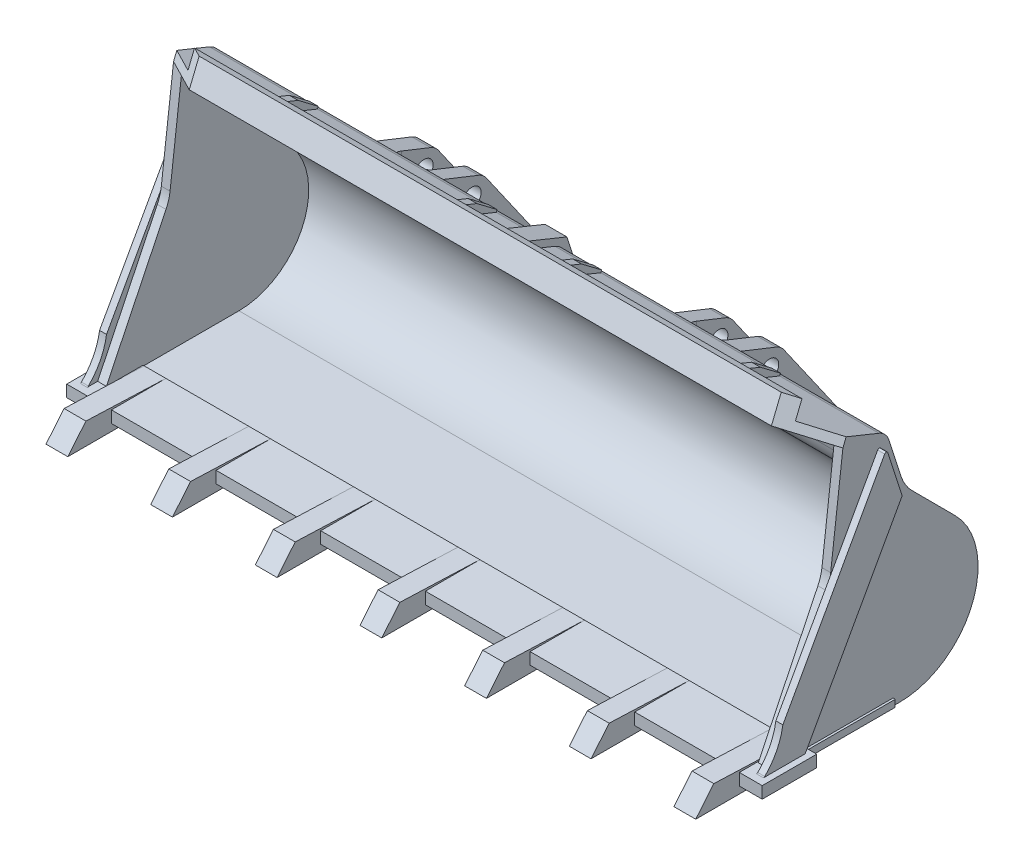
SolidWorks part; units mm, degrees
ref_plane "Front Plane" through (0, 0, 0) normal (0, 0, 1) x (1, 0, 0)
ref_plane "Top Plane" through (0, 0, 0) normal (0, 1, 0) x (1, 0, 0)
ref_plane "Right Plane" through (0, 0, 0) normal (1, 0, 0) x (0, 0, -1)
sketch "Sketch1" plane through (0, 0, 0) normal (1, 0, 0) x (0, 0, -1)
  line L0 (0, 0) -> (0, 1)
  line L1 (0, 1) -> (7.25, 16)
  line L2 (7.25, 16) -> (8.75, 28.5)
  line L3 (0, 0) -> (15.25, 0)
  line L4 (8.75, 28.5) -> (5.5533, 29.7974)
  line L5 (5.5533, 29.7974) -> (6.6814, 32.5772)
  line L6 (6.6814, 32.5772) -> (7.608, 32.2011)
  line L7 (7.608, 32.2011) -> (6.8559, 30.348)
  line L8 (6.8559, 30.348) -> (13.7401, 27.5539)
  line L9 (13.7401, 27.5539) -> (15.7923, 21.2039)
  line L10 (15.7923, 21.2039) -> (21.624, 15.3539)
  arc A0 (21.624, 15.3539) -> (15.25, 0) centre (15.25, 9) cw
  dimension "D15" = 9
  dimension "D1" = 1
  dimension "D2" = 7.25
  dimension "D3" = 16
  dimension "D4" = 28.5
  dimension "D5" = 8.75
  dimension "D6" = 15.25
  dimension "D7" = 2
  dimension "D8" = 1
  dimension "D9" = 3.45
  dimension "D10" = 1
  dimension "D11" = 130
  dimension "D12" = 153
  dimension "D13" = 6.35
  dimension "D14" = 5.85
extrude "Boss-Extrude1" add sketch "Sketch1" along normal blind 38.375
fillet "Fillet1" radius 5 1 edges at (19.1875, 21.2039, -15.7923)
fillet "Fillet2" radius 2 1 edges at (19.1875, 27.5539, -13.7401)
fillet "Fillet3" radius 5 1 edges at (19.1875, 16, -7.25)
shell "Shell1" thickness 1 removed face at (0, 19.8023, -10.049) removed face at (19.1875, 16.029, -7.1509) removed face at (19.1875, 22.6643, -8.0497) removed face at (19.1875, 8.1243, -3.4434) removed face at (19.1875, 0.5, 0)
sketch "Sketch3" plane through (0, 0, 0) normal (1, 0, 0) x (0, 0, -1)
  line L0 (0, 0) -> (15.25, 0) construction
  line L1 (4.25, 1.1) -> (-2, 1.1)
  line L2 (4.25, 1.1) -> (4.25, -0.25)
  line L3 (4.25, -0.25) -> (-2, -0.25)
  line L4 (-2, 1.1) -> (-2, -0.25)
  dimension "D1" = 2
  dimension "D2" = 1.35
  dimension "D3" = 6.25
  dimension "D4" = 0.25
extrude "Boss-Extrude2" add sketch "Sketch3" along normal blind 39.875
sketch "Sketch4" plane through (0, 0, 0) normal (1, 0, 0) x (0, 0, -1)
  line L1 (4.25, 0) -> (14.5, 0)
  line L2 (4.25, 0) -> (4.25, 0.8)
  line L3 (4.25, 0.8) -> (14.5, 0.8)
  line L4 (14.5, 0) -> (14.5, 0.8)
  dimension "D1" = 10.25
  dimension "D2" = 0.8
extrude "Boss-Extrude3" add sketch "Sketch4" along normal blind 38.625
sketch "Sketch5" plane through (38.375, 0, 0) normal (1, 0, 0) x (0, 0, -1)
  line L0 (-1.4, 0.8) -> (3.4593, 0.8)
  line L1 (3.4593, 0.8) -> (14.7517, 21.1721)
  line L2 (14.7517, 21.1721) -> (12.962, 26.7098)
  line L3 (12.962, 26.7098) -> (1.0667, 5.25)
  line L4 (15.4232, 22.3462) -> (14.0269, 26.6665) construction
  line L5 (-2, 1.1) -> (-2, -0.25) construction
  line L6 (4.25, 1.1) -> (-2, 1.1) construction
  line L8 (14.5, 0.8) -> (4.25, 0.8) construction
  line L9 (-1.4, 0.8) -> (1.0667, 5.25) construction
  arc A0 (1.0667, 5.25) -> (-1.4, 0.8) centre (-6.1511, 6.3423) cw
  dimension "D4" = 7.3
  dimension "D1" = 1
  dimension "D2" = 0.6
  dimension "D3" = 0.3
  dimension "D5" = 4.45
  dimension "D6" = 4.25
  dimension "D7" = 61
extrude "Boss-Extrude4" add sketch "Sketch5" along normal blind 0.8
fillet "Fillet4" radius 0.2 3 edges at (38.775, 1.1, 1.0709) (38.775, 21.1721, -14.7517) (38.775, 26.7098, -12.962)
sketch "Sketch6" plane through (0, 28.445, -11.5446) normal (0, 0.9266, -0.3761) x (1, 0, 0)
  line L0 (38.375, -2.6101) -> (33.375, -6.0601)
  line L1 (38.375, -6.0601) -> (0, -6.0601) construction
  line L2 (33.375, -6.0601) -> (38.375, -6.0601)
  line L3 (38.375, -6.0601) -> (38.375, -2.6101)
  dimension "D1" = 5
extrude "Cut-Extrude1" cut sketch "Sketch6" against normal up to next and the other way through all
sketch "Sketch7" plane through (0, 0, 0) normal (1, 0, 0) x (0, 0, -1)
  line L0 (9.1696, 29.4089) -> (9.4516, 30.1039)
  line L1 (9.4516, 30.1039) -> (14.2253, 28.1665)
  line L2 (14.2253, 28.1665) -> (15.568, 24.0118)
  line L3 (15.568, 24.0118) -> (14.9495, 23.8119)
  line L16 (4.25, 0) -> (15.25, 0)
  line L17 (4.25, -0.25) -> (4.25, 0)
  line L18 (-2, -0.25) -> (4.25, -0.25)
  line L19 (-2, 1.1) -> (-2, -0.25)
  line L20 (4.25, 1.1) -> (-2, 1.1)
  line L21 (4.25, 1) -> (4.25, 1.1)
  line L22 (15.25, 1) -> (4.25, 1)
  line L23 (15.9316, 19.6478) -> (20.9157, 14.648)
  line L24 (13.0754, 26.359) -> (14.4716, 22.0386)
  line L25 (5.5533, 29.7974) -> (12.4999, 26.9781)
  line L26 (6.6814, 32.5772) -> (5.5533, 29.7974)
  line L27 (7.608, 32.2011) -> (6.6814, 32.5772)
  line L28 (6.8559, 30.348) -> (7.608, 32.2011)
  line L29 (12.876, 27.9047) -> (6.8559, 30.348)
  line L30 (15.4232, 22.3462) -> (14.0269, 26.6665)
  line L31 (21.624, 15.3539) -> (16.6398, 20.3538)
  line L45 (12.876, 27.9047) -> (9.1696, 29.4089)
  line L46 (14.9495, 23.8119) -> (14.0269, 26.6665)
  arc A6 (15.25, 1) -> (20.9157, 14.648) centre (15.25, 9) ccw
  arc A7 (14.4716, 22.0386) -> (15.9316, 19.6478) centre (20.1809, 23.8838) ccw
  arc A8 (13.0754, 26.359) -> (12.4999, 26.9781) centre (12.1238, 26.0515) ccw
  arc A9 (14.0269, 26.6665) -> (12.876, 27.9047) centre (12.1238, 26.0515) ccw
  arc A10 (15.4232, 22.3462) -> (16.6398, 20.3538) centre (20.1809, 23.8838) ccw
  arc A11 (15.25, 0) -> (21.624, 15.3539) centre (15.25, 9) ccw
  arc A15 (14.0269, 26.6665) -> (12.876, 27.9047) centre (12.1238, 26.0515) ccw
  dimension "D2" = 0.75
  dimension "D3" = 0.65
  dimension "D4" = 4
  dimension "D5" = 3
  dimension "D1" = 0
extrude "Boss-Extrude5" add sketch "Sketch7" along normal blind 1.25
sketch "Sketch8" plane through (0, 28.445, -11.5446) normal (0, 0.9266, -0.3761) x (1, 0, 0)
  line L0 (38.375, 1.4368) -> (1.25, 1.4368) construction
  line L1 (5.5, 1.4368) -> (6.5, 1.4368)
  line L2 (5.5, 1.4368) -> (5.5, -5.0601)
  line L3 (5.5, -5.0601) -> (6.5, -5.0601)
  line L4 (6.5, 1.4368) -> (6.5, -5.0601)
  line L5 (34.8243, -5.0601) -> (0, -5.0601) construction
  line L6 (0, -2.5632) -> (0, -5.0601) construction
  line L7 (26, 1.4368) -> (27, 1.4368)
  line L8 (26, 1.4368) -> (26, -5.0601)
  line L9 (26, -5.0601) -> (27, -5.0601)
  line L10 (27, 1.4368) -> (27, -5.0601)
  dimension "D1" = 1
  dimension "D2" = 5.5
  dimension "D3" = 20.5
  dimension "D4" = 1
extrude "Boss-Extrude6" add sketch "Sketch8" along normal blind 1
chamfer "Chamfer1" distance 0.75 angle 75 2 edges at (26.5, 28.8313, -13.252) (6, 28.8313, -13.252) first distance on face at (26.5, 28.368, -13.064) first distance on face at (6, 28.368, -13.064)
mirror "Mirror1" about plane through (0, 0, 0) normal (1, 0, 0) of bodies 107
sketch "Sketch9" plane through (0, 0, 0) normal (1, 0, 0) x (0, 0, -1)
  line L0 (4.25, -0.25) -> (4.25, 1.1) construction
  line L2 (4.25, 0) -> (14.5, 0) construction
  line L3 (14.5, 0) -> (15.25, 0) construction
  line L4 (21.624, 15.3539) -> (16.6398, 20.3538) construction
  line L5 (15.4232, 22.3462) -> (14.0269, 26.6665) construction
  line L6 (4.25, -0.125) -> (4.25, 0)
  line L8 (4.25, 0) -> (14.5, 0)
  line L9 (14.5, 0) -> (15.25, 0)
  line L10 (21.624, 15.3539) -> (16.6398, 20.3538)
  line L11 (15.4232, 22.3462) -> (14.0269, 26.6665)
  line L13 (4.25, -0.125) -> (27.5244, -0.125)
  line L14 (29.0098, 1.5838) -> (27.6069, 11.5632)
  line L15 (26.755, 13.7297) -> (19.4824, 24.1446)
  line L16 (18.5807, 24.8584) -> (14.0269, 26.6665)
  arc A0 (15.25, 0) -> (21.624, 15.3539) centre (15.25, 9) ccw construction
  arc A1 (15.4232, 22.3462) -> (16.6398, 20.3538) centre (20.1809, 23.8838) ccw construction
  arc A3 (15.25, 0) -> (21.624, 15.3539) centre (15.25, 9) ccw
  arc A4 (15.4232, 22.3462) -> (16.6398, 20.3538) centre (20.1809, 23.8838) ccw
  arc A6 (27.6069, 11.5632) -> (26.755, 13.7297) centre (22.6556, 10.8671) ccw
  arc A7 (19.4824, 24.1446) -> (18.5807, 24.8584) centre (17.8426, 22.9996) ccw
  arc A8 (27.5244, -0.125) -> (29.0098, 1.5838) centre (27.5244, 1.375) ccw
  point P20 (27.4403, 12.7484)
  point P23 (19.1387, 24.6368)
  point P26 (29.25, -0.125)
  dimension "D6" = 5
  dimension "D7" = 2
  dimension "D8" = 1.5
  dimension "D1" = 5.5
  dimension "D2" = 25
  dimension "D3" = 0.125
  dimension "D4" = 13
  dimension "D5" = 14.5
extrude "Boss-Extrude7" add sketch "Sketch9" along normal mid plane 41.75 separate body
sketch "Sketch10" plane through (0, 0, 0) normal (0, 1, 0) x (1, 0, 0)
  line L0 (0, -14.2861) -> (0, 38.0554) construction
  line L1 (-15.05, 39.2344) -> (-18.75, 39.2344)
  line L2 (-13.25, 39.2344) -> (13.25, 39.2344)
  line L3 (-13.25, 39.2344) -> (-13.25, -0.3739)
  line L4 (-13.25, -0.3739) -> (13.25, -0.3739)
  line L5 (13.25, 39.2344) -> (13.25, -0.3739)
  line L6 (-13.25, 39.2344) -> (13.25, -0.3739) construction
  line L7 (-13.25, -0.3739) -> (13.25, 39.2344) construction
  line L8 (-37.375, 13.0754) -> (37.375, 13.0754) construction
  line L9 (15.05, 15.2754) -> (15.05, 39.2344)
  line L10 (15.05, 39.2344) -> (18.75, 39.2344)
  line L11 (18.75, 15.2754) -> (18.75, 39.2344)
  line L12 (-18.75, 15.2754) -> (-18.75, 39.2344)
  line L13 (20.875, 27.5244) -> (-20.875, 27.5244) construction
  line L14 (-15.05, 15.2754) -> (-15.05, 39.2344)
  arc A0 (-15.05, 15.2754) -> (-18.75, 15.2754) centre (-16.9, 15.2754) cw
  arc A1 (18.75, 15.2754) -> (15.05, 15.2754) centre (16.9, 15.2754) cw
  point P3 (0, 19.4302)
  point P20 (16.9, 13.4254)
  dimension "D4" = 1.85
  dimension "D5" = 0.35
  dimension "D1" = 37.5
  dimension "D2" = 30.1
  dimension "D3" = 26.5
  dimension "D6" = 11.71
extrude "Cut-Extrude2" cut sketch "Sketch10" against normal blind 41.75 and the other way through all
sketch "Sketch11" plane through (0, 0, 0) normal (1, 0, 0) x (0, 0, -1)
  circle A0 centre (27.5244, 1.375) radius 1.05
  circle A1 centre (17.8426, 22.9996) radius 1.05
  dimension "D1" = 2.1
  dimension "D2" = 2.1
extrude "Cut-Extrude3" cut sketch "Sketch11" against normal through all both and the other way through all
combine bodies "Combine1" operation type add bodies to combine 108 112 113
sketch "Sketch12" plane through (0, 0, 0) normal (1, 0, 0) x (0, 0, -1)
  line L0 (4.25, 1.1) -> (3.75, -0.25)
  line L1 (-2, -0.25) -> (4.25, -0.25) construction
  line L2 (3.75, -0.25) -> (3.75, -1.05)
  line L3 (-7, -1.05) -> (-4.9233, 1.45)
  line L4 (-4.9233, 1.45) -> (4.25, 1.1)
  line L5 (-7, -1.05) -> (3.75, -1.05)
  line L6 (-2, 1.1) -> (-2, -0.25) construction
  dimension "D1" = 3.25
  dimension "D2" = 5
  dimension "D3" = 2.5
  dimension "D4" = 90
  dimension "D5" = 0.5
  dimension "D6" = 0.8
extrude "Boss-Extrude8" add sketch "Sketch12" along normal mid plane 2.5
pattern_linear "LPattern2" count 4 spacing 12 along (1, 0, 0) count 4 spacing 12 along (-1, 0, 0) of "Boss-Extrude8"
